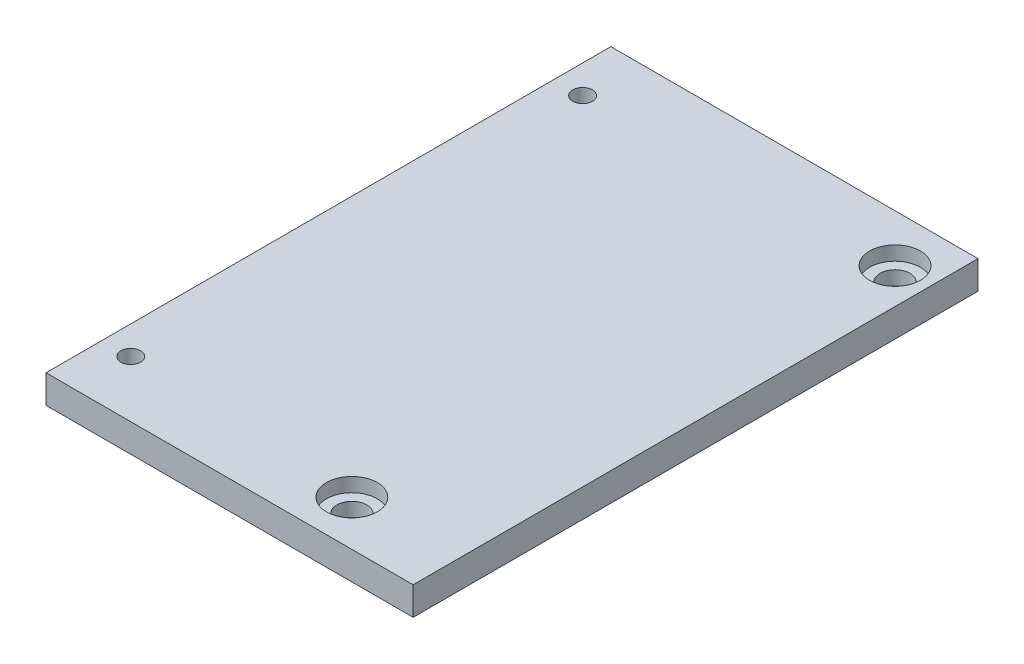
SolidWorks part; units mm, degrees
ref_plane "Front Plane" through (0, 0, 0) normal (0, 0, 1) x (1, 0, 0)
ref_plane "Top Plane" through (0, 0, 0) normal (0, 1, 0) x (1, 0, 0)
ref_plane "Right Plane" through (0, 0, 0) normal (1, 0, 0) x (0, 0, -1)
sketch "Sketch2" plane through (0, 0, 0) normal (0, 1, 0) x (1, 0, 0)
  line L1 (-32.5, 50) -> (32.5, 50)
  line L2 (-32.5, 50) -> (-32.5, -50)
  line L3 (-32.5, -50) -> (32.5, -50)
  line L4 (32.5, 50) -> (32.5, -50)
  line L5 (-32.5, 50) -> (32.5, -50) construction
  line L6 (-32.5, -50) -> (32.5, 50) construction
  circle A0 centre (-27.5, 40) radius 1.75
  circle A1 centre (-27.5, -40) radius 1.75
  circle A2 centre (26.23, 41.58) radius 2.65
  circle A3 centre (13.65, -42) radius 2.65
  point P0 (0, 0)
  dimension "D3" = 3.5
  dimension "D4" = 5
  dimension "D8" = 5.3
  dimension "D9" = 5.3
  dimension "D1" = 65
  dimension "D2" = 100
  dimension "D5" = 5
  dimension "D6" = 10
  dimension "D7" = 10
  dimension "D10" = 46.15
  dimension "D11" = 8
  dimension "D12" = 8.42
  dimension "D13" = 6.27
extrude "Boss-Extrude1" add sketch "Sketch2" along normal blind 5
sketch "Sketch3" plane through (0, 5, 0) normal (0, 1, 0) x (1, 0, 0)
  circle A0 centre (26.23, 41.58) radius 4.5
  circle A1 centre (13.65, -42) radius 4.5
  dimension "D1" = 9
  dimension "D2" = 9
extrude "Cut-Extrude1" cut sketch "Sketch3" against normal blind 2.5
